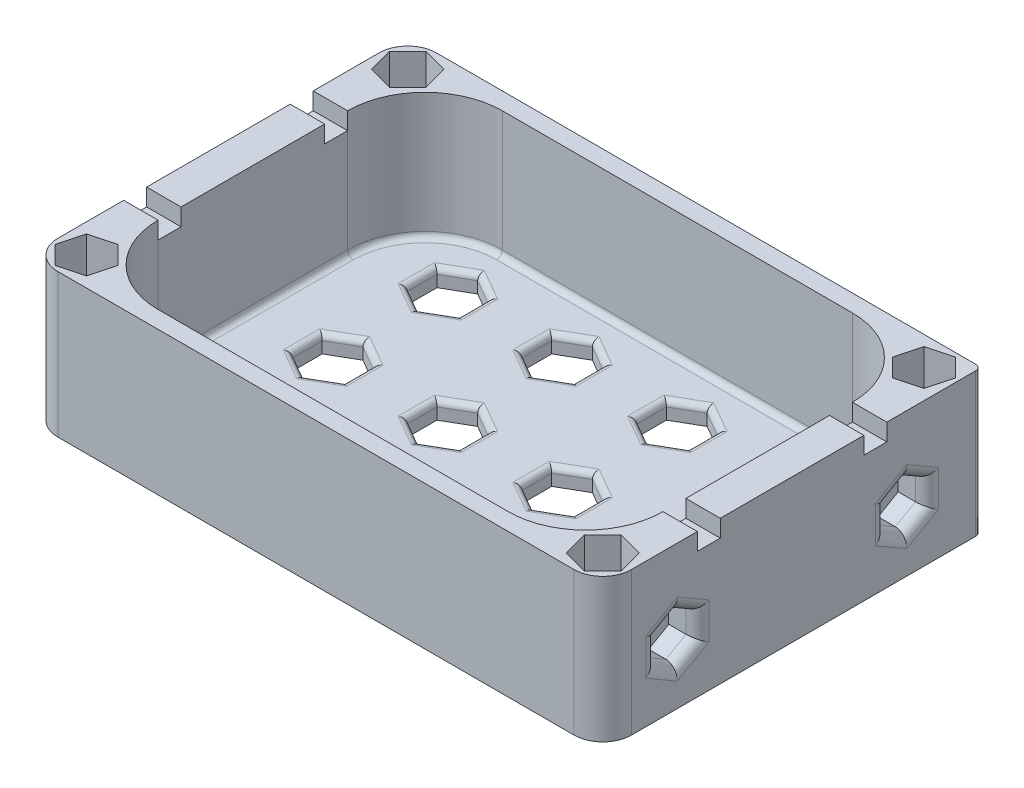
SolidWorks part; units mm, degrees
note: The reader was unsure of these and kept them because the rebuilt part matched: shared geometry of "Sketch3<7>".
ref_plane "Front Plane" through (0, 0, 0) normal (0, 0, 1) x (1, 0, 0)
ref_plane "Top Plane" through (0, 0, 0) normal (0, 1, 0) x (1, 0, 0)
ref_plane "Right Plane" through (0, 0, 0) normal (1, 0, 0) x (0, 0, -1)
sketch "Sketch3" plane through (0, 0, 0) normal (0, -1, 0) x (1, 0, 0)
  line L0 (-60, 20) -> (-80, 20)
  line L1 (-90, 23) -> (-100, 23)
  line L2 (-80, -5.1962) -> (-75.5, -2.5981)
  line L3 (-90, -23) -> (-100, -23)
  line L4 (-6, 23) -> (-6, -23)
  line L5 (-60, 0) -> (-40, 0)
  line L6 (-94, 23) -> (-94, -23)
  line L7 (-75.5, -2.5981) -> (-75.5, 2.5981)
  line L8 (-75.5, 2.5981) -> (-80, 5.1962)
  line L9 (-80, 5.1962) -> (-84.5, 2.5981)
  line L10 (-84.5, 2.5981) -> (-84.5, -2.5981)
  line L11 (-100, -23) -> (-100, -33)
  line L12 (-100, 23) -> (-100, 33)
  line L13 (-100, 33) -> (-10, 33)
  line L14 (-10, 33) -> (0, 33)
  line L15 (0, 33) -> (0, -23)
  line L16 (-90, 23) -> (-90, 33)
  line L17 (0, 33) -> (0, 23)
  line L18 (0, 23) -> (-10, 23)
  line L19 (-100, -33) -> (-10, -33)
  line L20 (-10, -33) -> (-10, -23)
  line L21 (-10, -33) -> (0, -33)
  line L22 (0, -33) -> (0, -23)
  line L23 (-10, 23) -> (-10, 33)
  line L24 (-90, -23) -> (-90, -33)
  line L49 (-10, -23) -> (0, -23)
  line L50 (-100, 33) -> (-90, 23)
  line L65 (0, 33) -> (-10, 23)
  line L67 (0, -33) -> (-10, -23)
  line L69 (-90, -23) -> (-100, -33)
  line L76 (-90, 30) -> (-10, 30)
  line L83 (-90, -30) -> (-10, -30)
  line L84 (-84.5, -2.5981) -> (-80, -5.1962)
  line L85 (-40, 0) -> (-20, 0)
  line L86 (-20, 0) -> (-20, 20)
  line L87 (-20, -20) -> (-20, 0)
  line L88 (-60, -20) -> (-40, -20)
  line L89 (-40, -20) -> (-20, -20)
  line L90 (-60, -20) -> (-60, 0)
  line L91 (-60, 20) -> (-40, 20)
  line L92 (-40, 20) -> (-20, 20)
  line L93 (-60, 0) -> (-60, 20)
  line L94 (-40, 20) -> (-40, 0)
  line L95 (-40, 0) -> (-40, -20)
  line L96 (0, 23) -> (0, -23)
  line L97 (0, 0) -> (-20, 0)
  line L98 (-80, -25.1962) -> (-75.5, -22.5981)
  line L99 (-55.5, 17.4019) -> (-55.5, 22.5981)
  line L100 (-55.5, 22.5981) -> (-60, 25.1962)
  line L101 (-60, 25.1962) -> (-64.5, 22.5981)
  line L102 (-64.5, 22.5981) -> (-64.5, 17.4019)
  line L103 (-64.5, 17.4019) -> (-60, 14.8038)
  line L104 (-60, 14.8038) -> (-55.5, 17.4019)
  line L105 (-35.5, 17.4019) -> (-35.5, 22.5981)
  line L106 (-35.5, 22.5981) -> (-40, 25.1962)
  line L107 (-40, 25.1962) -> (-44.5, 22.5981)
  line L108 (-44.5, 22.5981) -> (-44.5, 17.4019)
  line L109 (-44.5, 17.4019) -> (-40, 14.8038)
  line L110 (-40, 14.8038) -> (-35.5, 17.4019)
  line L111 (-24.5, 17.4019) -> (-20, 14.8038)
  line L112 (-20, 14.8038) -> (-15.5, 17.4019)
  line L113 (-15.5, 17.4019) -> (-15.5, 22.5981)
  line L114 (-15.5, 22.5981) -> (-20, 25.1962)
  line L115 (-20, 25.1962) -> (-24.5, 22.5981)
  line L116 (-24.5, 22.5981) -> (-24.5, 17.4019)
  line L117 (-24.5, 2.5981) -> (-24.5, -2.5981)
  line L118 (-24.5, -2.5981) -> (-20, -5.1962)
  line L119 (-20, -5.1962) -> (-15.5, -2.5981)
  line L120 (-15.5, -2.5981) -> (-15.5, 2.5981)
  line L121 (-15.5, 2.5981) -> (-20, 5.1962)
  line L122 (-20, 5.1962) -> (-24.5, 2.5981)
  line L123 (-40, 5.1962) -> (-44.5, 2.5981)
  line L124 (-44.5, 2.5981) -> (-44.5, -2.5981)
  line L125 (-44.5, -2.5981) -> (-40, -5.1962)
  line L126 (-40, -5.1962) -> (-35.5, -2.5981)
  line L127 (-35.5, -2.5981) -> (-35.5, 2.5981)
  line L128 (-35.5, 2.5981) -> (-40, 5.1962)
  line L129 (-60, 5.1962) -> (-64.5, 2.5981)
  line L130 (-64.5, 2.5981) -> (-64.5, -2.5981)
  line L131 (-64.5, -2.5981) -> (-60, -5.1962)
  line L132 (-60, -5.1962) -> (-55.5, -2.5981)
  line L133 (-55.5, -2.5981) -> (-55.5, 2.5981)
  line L134 (-55.5, 2.5981) -> (-60, 5.1962)
  line L135 (-64.5, -17.4019) -> (-64.5, -22.5981)
  line L136 (-64.5, -22.5981) -> (-60, -25.1962)
  line L137 (-60, -25.1962) -> (-55.5, -22.5981)
  line L138 (-55.5, -22.5981) -> (-55.5, -17.4019)
  line L139 (-55.5, -17.4019) -> (-60, -14.8038)
  line L140 (-60, -14.8038) -> (-64.5, -17.4019)
  line L141 (-44.5, -22.5981) -> (-40, -25.1962)
  line L142 (-40, -25.1962) -> (-35.5, -22.5981)
  line L143 (-35.5, -22.5981) -> (-35.5, -17.4019)
  line L144 (-35.5, -17.4019) -> (-40, -14.8038)
  line L145 (-40, -14.8038) -> (-44.5, -17.4019)
  line L146 (-44.5, -17.4019) -> (-44.5, -22.5981)
  line L147 (-20, -25.1962) -> (-15.5, -22.5981)
  line L148 (-15.5, -22.5981) -> (-15.5, -17.4019)
  line L149 (-15.5, -17.4019) -> (-20, -14.8038)
  line L150 (-20, -14.8038) -> (-24.5, -17.4019)
  line L151 (-24.5, -17.4019) -> (-24.5, -22.5981)
  line L152 (-24.5, -22.5981) -> (-20, -25.1962)
  line L153 (-8.1639, 31.1639) -> (-9.322, 26.8419)
  line L154 (-9.322, 26.8419) -> (-6.1581, 23.678)
  line L155 (-6.1581, 23.678) -> (-1.8361, 24.8361)
  line L156 (-1.8361, 24.8361) -> (-0.678, 29.1581)
  line L157 (-0.678, 29.1581) -> (-3.8419, 32.322)
  line L158 (-3.8419, 32.322) -> (-8.1639, 31.1639)
  line L165 (-99.322, -29.1581) -> (-96.1581, -32.322)
  line L166 (-96.1581, -32.322) -> (-91.8361, -31.1639)
  line L167 (-91.8361, -31.1639) -> (-90.678, -26.8419)
  line L168 (-90.678, -26.8419) -> (-93.8419, -23.678)
  line L169 (-93.8419, -23.678) -> (-98.1639, -24.8361)
  line L170 (-98.1639, -24.8361) -> (-99.322, -29.1581)
  line L171 (-1.8361, -24.8361) -> (-6.1581, -23.678)
  line L172 (-6.1581, -23.678) -> (-9.322, -26.8419)
  line L173 (-9.322, -26.8419) -> (-8.1639, -31.1639)
  line L174 (-8.1639, -31.1639) -> (-3.8419, -32.322)
  line L175 (-3.8419, -32.322) -> (-0.678, -29.1581)
  line L176 (-0.678, -29.1581) -> (-1.8361, -24.8361)
  line L183 (-99.322, 29.1581) -> (-98.1639, 24.8361)
  line L184 (-98.1639, 24.8361) -> (-93.8419, 23.678)
  line L185 (-93.8419, 23.678) -> (-90.678, 26.8419)
  line L186 (-90.678, 26.8419) -> (-91.8361, 31.1639)
  line L187 (-91.8361, 31.1639) -> (-96.1581, 32.322)
  line L188 (-96.1581, 32.322) -> (-99.322, 29.1581)
  line L189 (-75.5, -22.5981) -> (-75.5, -17.4019)
  line L190 (-100, -23) -> (-100, 23)
  line L191 (-75.5, -17.4019) -> (-80, -14.8038)
  line L192 (-80, -14.8038) -> (-84.5, -17.4019)
  line L193 (-84.5, -17.4019) -> (-84.5, -22.5981)
  line L194 (-84.5, -22.5981) -> (-80, -25.1962)
  line L195 (-80, 25.1962) -> (-84.5, 22.5981)
  line L196 (-84.5, 22.5981) -> (-84.5, 17.4019)
  line L197 (-84.5, 17.4019) -> (-80, 14.8038)
  line L198 (-80, 14.8038) -> (-75.5, 17.4019)
  line L199 (-75.5, 17.4019) -> (-75.5, 22.5981)
  line L200 (-75.5, 22.5981) -> (-80, 25.1962)
  line L201 (-80, 20) -> (-80, 0)
  line L202 (-80, 0) -> (-80, -20)
  line L203 (-80, -20) -> (-60, -20)
  line L204 (-60, 0) -> (-80, 0)
  arc A2 (-6, -16.5167) -> (-19.4833, -30) centre (-19.4833, -16.5167) cw
  circle A3 centre (-5, 28) radius 5
  circle A4 centre (-5, -28) radius 5
  circle A6 centre (-95, 28) radius 5
  circle A8 centre (-95, -28) radius 5
  arc A11 (-19.4833, 30) -> (-6, 16.5167) centre (-19.4833, 16.5167) cw
  circle A12 centre (-60, 20) radius 4.5
  circle A13 centre (-40, 20) radius 4.5
  arc A14 (-94, 16.5167) -> (-80.5167, 30) centre (-80.5167, 16.5167) cw
  arc A15 (-94, -16.5167) -> (-80.5167, -30) centre (-80.5167, -16.5167) ccw
  circle A16 centre (-95, 28) radius 3.875
  circle A17 centre (-5, 28) radius 3.875
  circle A18 centre (-5, -28) radius 3.875
  circle A19 centre (-95, -28) radius 3.875
  circle A20 centre (-20, 20) radius 4.5
  circle A21 centre (-20, -20) radius 4.5
  circle A22 centre (-40, -20) radius 4.5
  circle A23 centre (-60, -20) radius 4.5
  circle A24 centre (-60, 0) radius 4.5
  circle A25 centre (-40, 0) radius 4.5
  circle A26 centre (-20, 0) radius 4.5
  circle A27 centre (-60, 20) radius 4.5 construction
  circle A28 centre (-40, 20) radius 4.5 construction
  circle A29 centre (-20, 20) radius 4.5 construction
  circle A30 centre (-20, 0) radius 4.5 construction
  circle A31 centre (-40, 0) radius 4.5 construction
  circle A32 centre (-60, 0) radius 4.5 construction
  circle A33 centre (-60, -20) radius 4.5 construction
  circle A34 centre (-40, -20) radius 4.5 construction
  circle A35 centre (-20, -20) radius 4.5 construction
  circle A36 centre (-5, 28) radius 3.875 construction
  circle A37 centre (-95, 28) radius 3.875 construction
  circle A38 centre (-95, -28) radius 3.875 construction
  circle A39 centre (-5, -28) radius 3.875 construction
  circle A40 centre (-80, 0) radius 4.5 construction
  circle A41 centre (-80, -20) radius 4.5 construction
  circle A42 centre (-80, 20) radius 4.5 construction
  dimension "D5" = 3
  dimension "D3" = 10
  dimension "D8" = 9
  dimension "D4" = 7.75
  dimension "D9" = 20
  dimension "D12" = 100
  dimension "D1" = 6
  dimension "D2" = 3
  dimension "D6" = 60
  dimension "D7" = 6
  dimension "D10" = 20
  dimension "D11" = 20
extrude "Boss-Extrude7" add sketch "Sketch3" against normal blind 25 contours L21 A4 L67 | L67 A4 L22 | A4 L67 L175 L176 L171 L172 | A4 L67 L172 L173 L174 L175 | L22 A4 L49 | L49 A4 L67 A2 | A2 A4 L20 | L67 A4 A2 | L20 A4 L21 | A2 L20 L83 | L24 L83 L20 L19 | L97 L96 L49 L4 | A2 L4 L49 | L15 L97 L4 L18 | A11 L18 L4 | A11 L65 A3 L18 | A11 L23 A3 | A11 L76 L23 | A11 A3 L65 | A3 L65 L157 L158 L153 L154 | A3 L65 L154 L155 L156 L157 | L18 A3 L17 | L76 L16 L13 L23 | L14 A3 L23 | L24 A15 L83 | L19 A8 L24 | A8 L69 L165 L166 L167 L168 | A8 L69 L168 L169 L170 L165 | L3 A8 L11 | L69 A15 A8 | L3 A15 L69 A8 | A8 A15 L24 | L3 L190 L1 L6 | L6 A15 L3 | A14 L6 L1 | A14 L1 A6 L50 | A14 L50 A6 | A14 A6 L16 | A6 L50 L185 L186 L187 L188 | A6 L50 L188 L183 L184 L185 | L12 A6 L1 | L16 A6 L13 | A14 L16 L76
extrude "Boss-Extrude9" add sketch "Sketch3<7>" against normal blind 3
sketch "Sketch3<7>" plane through (0, 0, 0) normal (0, -1, 0) x (1, 0, 0) same geometry as "Sketch3"
sketch "Sketch5" plane through (-100, 0, 0) normal (-1, 0, 0) x (0, 0, 1)
  line L1 (-20, 6.4585) -> (-16.5, 8.4793)
  line L2 (-16.5, 8.4793) -> (-16.5, 12.5207)
  line L3 (-16.5, 12.5207) -> (-20, 14.5415)
  line L4 (-20, 14.5415) -> (-23.5, 12.5207)
  line L5 (-23.5, 12.5207) -> (-23.5, 8.4793)
  line L6 (-23.5, 8.4793) -> (-20, 6.4585)
  line L7 (23.5, 8.4793) -> (23.5, 12.5207)
  line L8 (23.5, 12.5207) -> (20, 14.5415)
  line L9 (20, 14.5415) -> (16.5, 12.5207)
  line L10 (16.5, 12.5207) -> (16.5, 8.4793)
  line L11 (16.5, 8.4793) -> (20, 6.4585)
  line L12 (20, 6.4585) -> (23.5, 8.4793)
  line L13 (-20, 10.5) -> (20, 10.5)
  line L18 (0, 0) -> (0, 10.5)
  line L19 (-28, 0) -> (28, 0) construction
  circle A0 centre (-20, 10.5) radius 3.5 construction
  circle A1 centre (20, 10.5) radius 3.5 construction
  circle A2 centre (-20, 10.5) radius 3.5
  circle A3 centre (20, 10.5) radius 3.5
  point P20 (0, 0)
  point P30 (0, 0)
  dimension "D3" = 7
  dimension "D1" = 40
  dimension "D2" = 10.5
extrude "Cut-Extrude1" cut sketch "Sketch5" against normal blind 5
sketch "Sketch6" plane through (0, 0, 0) normal (1, 0, 0) x (0, 0, -1)
  line L1 (-20, 6.4585) -> (-16.5, 8.4793)
  line L2 (-16.5, 8.4793) -> (-16.5, 12.5207)
  line L3 (-16.5, 12.5207) -> (-20, 14.5415)
  line L4 (-20, 14.5415) -> (-23.5, 12.5207)
  line L5 (-23.5, 12.5207) -> (-23.5, 8.4793)
  line L6 (-23.5, 8.4793) -> (-20, 6.4585)
  line L7 (20, 6.4585) -> (23.5, 8.4793)
  line L8 (23.5, 8.4793) -> (23.5, 12.5207)
  line L9 (23.5, 12.5207) -> (20, 14.5415)
  line L10 (20, 14.5415) -> (16.5, 12.5207)
  line L11 (16.5, 12.5207) -> (16.5, 8.4793)
  line L12 (16.5, 8.4793) -> (20, 6.4585)
  line L15 (0, 0) -> (0, 10.5)
  line L16 (-20, 10.5) -> (20, 10.5)
  circle A0 centre (-20, 10.5) radius 3.5 construction
  circle A1 centre (20, 10.5) radius 3.5 construction
  circle A2 centre (-20, 10.5) radius 3.5
  circle A3 centre (20, 10.5) radius 3.5
  dimension "D1" = 7
  dimension "D2" = 40
  dimension "D3" = 10.5
extrude "Cut-Extrude2" cut sketch "Sketch6" against normal blind 5 contours L4 L5 L6 L1 L2 L3 | L10 L11 L12 L7 L8 L9
fillet "Fillet3" radius 2 24 edges at (0, 10.5, -16.5) (0, 7.4689, -18.25) (0, 7.4689, -21.75) (0, 10.5, -23.5) (0, 13.5311, -21.75) (0, 13.5311, -18.25) (0, 7.4689, 21.75) (0, 10.5, 23.5) (0, 13.5311, 21.75) (0, 13.5311, 18.25) (0, 10.5, 16.5) (0, 7.4689, 18.25) (-100, 13.5311, 18.25) (-100, 7.4689, 21.75) (-100, 10.5, 23.5) (-100, 13.5311, 21.75) (-100, 10.5, 16.5) (-100, 7.4689, 18.25) (-100, 7.4689, -18.25) (-100, 10.5, -16.5) (-100, 13.5311, -21.75) (-100, 13.5311, -18.25) (-100, 10.5, -23.5) (-100, 7.4689, -21.75)
fillet "Fillet2" radius 1 1 edges at (0, 12.5, -33)
fillet "Fillet4" radius 1 44 edges at (-50, 3, -30) (-90.0508, 3, -26.0508) (-94, 3, 0) (-44.5, 3, 0) (-35.5, 3, 0) (-55.5, 3, 20) (-64.5, 3, 20) (-75.5, 3, 0) (-82.25, 3, 3.8971) (-84.5, 3, 0) (-82.25, 3, -3.8971) (-55.5, 3, 0) (-64.5, 3, 0) (-35.5, 3, 20) (-44.5, 3, 20) (-44.5, 3, -20) (-35.5, 3, -20) (-24.5, 3, 0) (-17.75, 3, -3.8971) (-15.5, 3, 0) (-17.75, 3, 3.8971) (-90.0508, 3, 26.0508) (-50, 3, 30) (-9.9492, 3, 26.0508) (-6, 3, 0) (-9.9492, 3, -26.0508) (-17.75, 3, 16.1029) (-15.5, 3, 20) (-17.75, 3, 23.8971) (-24.5, 3, 20) (-75.5, 3, 20) (-82.25, 3, 23.8971) (-84.5, 3, 20) (-82.25, 3, 16.1029) (-82.25, 3, -16.1029) (-84.5, 3, -20) (-82.25, 3, -23.8971) (-75.5, 3, -20) (-24.5, 3, -20) (-17.75, 3, -23.8971) (-15.5, 3, -20) (-17.75, 3, -16.1029) (-64.5, 3, -20) (-55.5, 3, -20)
sketch "Sketch7" plane through (0, 25, 0) normal (0, 1, 0) x (1, 0, 0)
  line L0 (-100, 28) -> (-100, -28) construction
  line L1 (-100, 16.5167) -> (-94, 16.5167)
  line L2 (-100, 16.5167) -> (-100, 12.5167)
  line L3 (-100, 12.5167) -> (-94, 12.5167)
  line L4 (-94, 16.5167) -> (-94, 12.5167)
  line L5 (-94, -16.5167) -> (-94, 16.5167) construction
  line L6 (0, -28) -> (0, 32) construction
  line L7 (-100, -12.5167) -> (-94, -12.5167)
  line L8 (-100, -12.5167) -> (-100, -16.5167)
  line L9 (-100, -16.5167) -> (-94, -16.5167)
  line L10 (-94, -12.5167) -> (-94, -16.5167)
  line L11 (0, 16.5167) -> (-6, 16.5167)
  line L12 (0, 16.5167) -> (0, 12.5167)
  line L13 (0, 12.5167) -> (-6, 12.5167)
  line L14 (-6, 16.5167) -> (-6, 12.5167)
  line L15 (-6, -16.5167) -> (-6, 16.5167) construction
  line L16 (0, -16.5167) -> (-6, -16.5167)
  line L17 (0, -16.5167) -> (0, -12.5167)
  line L18 (0, -12.5167) -> (-6, -12.5167)
  line L19 (-6, -16.5167) -> (-6, -12.5167)
  line L20 (-6, 16.5167) -> (-6, -16.5167) construction
  line L21 (-94, -16.5167) -> (-94, 16.5167) construction
  point P28 (0, 0)
  point P31 (0, 0)
  point P32 (0, 0)
  point P34 (0, 0)
  point P36 (0, 0)
  dimension "D1" = 4
extrude "Cut-Extrude3" cut sketch "Sketch7" against normal blind 3
